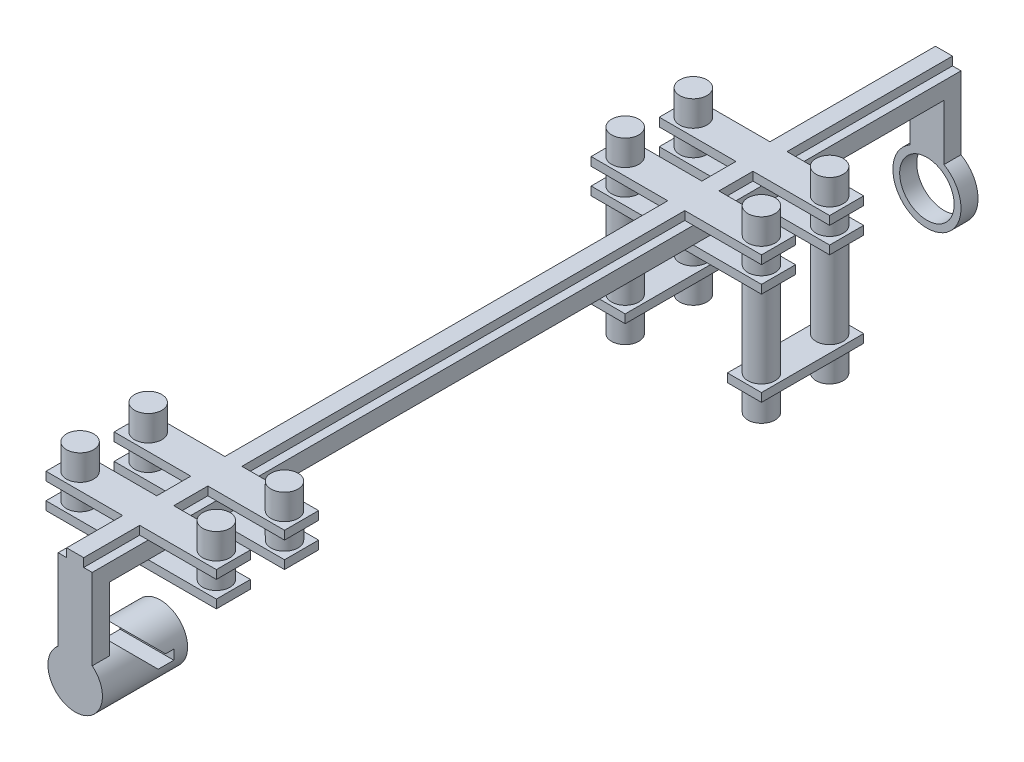
SolidWorks part; units mm, degrees
note: The reader was unsure of these and kept them because the rebuilt part matched: shared geometry of "Sketch9<2>", "Sketch11<2>".
ref_plane "Front Plane" through (0, 0, 0) normal (0, 0, 1) x (1, 0, 0)
ref_plane "Top Plane" through (0, 0, 0) normal (0, 1, 0) x (1, 0, 0)
ref_plane "Right Plane" through (0, 0, 0) normal (1, 0, 0) x (0, 0, -1)
sketch "Sketch1" plane through (0, 0, 0) normal (0, 0, 1) x (1, 0, 0)
  line L0 (0, 10) -> (0, 30)
  line L1 (-5, 30) -> (5, 30)
  line L2 (5, 30) -> (5, 8.6603)
  line L3 (-5, 30) -> (-5, 8.6603)
  circle A0 centre (0, 0) radius 8
  circle A1 centre (0, 0) radius 10
  point P8 (0, 30)
  dimension "D1" = 16
  dimension "D2" = 20
  dimension "D3" = 20
  dimension "D4" = 10
extrude "Boss-Extrude1" add sketch "Sketch1" along normal blind 5 contours A1 A0 | A1 L0 L1 L3 | A1 L2 L1 L0
sketch "Sketch2" plane through (0, 0, 5) normal (0, 0, 1) x (1, 0, 0)
  line L0 (5, 30) -> (5, 8.6603) construction
  line L1 (-5, 30) -> (5, 30)
  line L2 (-5, 30) -> (-5, 25)
  line L3 (-5, 25) -> (5, 25)
  line L4 (5, 30) -> (5, 25)
  dimension "D1" = 5
extrude "Boss-Extrude2" add sketch "Sketch2" along normal blind 250
sketch "Sketch4" plane through (0, 0, 255) normal (0, 0, 1) x (1, 0, 0)
  line L0 (-5, 25) -> (5, 25)
  line L1 (5, 25) -> (5, 6.245)
  line L2 (-5, 25) -> (-5, 6.245)
  arc A0 (-5, 6.245) -> (5, 6.245) centre (0, 0) ccw
extrude "Boss-Extrude3" add sketch "Sketch4" against normal blind 5
sketch "Sketch5" plane through (0, 0, 250) normal (0, 0, -1) x (-1, 0, 0)
  circle A0 centre (0, 0) radius 8
extrude "Boss-Extrude4" add sketch "Sketch5" along normal blind 20
sketch "Sketch6" plane through (0, 0, 0) normal (1, 0, 0) x (0, 0, -1)
  line L0 (-248.5853, 8.66) -> (-243.5853, 8.66)
  line L1 (-243.5853, 8.66) -> (-234.9253, 0)
  line L2 (-248.5853, 8.66) -> (-239.9253, 0)
  line L3 (-240.6367, 0) -> (-237.6205, 0) construction
  line L4 (-239.9253, 0) -> (-238.5099, -1.4155)
  line L5 (-239.9253, 1.4155) -> (-233.9253, 1.4155)
  line L6 (-239.9253, 1.4155) -> (-239.9253, -1.4155)
  line L7 (-239.9253, -1.4155) -> (-233.9253, -1.4155)
  line L8 (-233.9253, 1.4155) -> (-233.9253, -1.4155)
  point P5 (-239.9253, 0)
  dimension "D1" = 5
  dimension "D2" = 45
  dimension "D3" = 1
extrude "Cut-Extrude1" cut sketch "Sketch6" against normal through all both and the other way through all contours L3 L4 L7 L8 | L6 L5 L1 L0 L2 | L1 L3 L8 L5 | L6 L3 L1 L5
sketch "Sketch7" plane through (0, 25, 0) normal (0, -1, 0) x (1, 0, 0)
  line L3 (2.5, 19.6513) -> (5, 19.6513) construction
  line L4 (-2.5, 255) -> (2.5, 255)
  line L5 (-2.5, 255) -> (-2.5, 0)
  line L6 (-2.5, 0) -> (2.5, 0)
  line L7 (2.5, 255) -> (2.5, 0)
  line L8 (5, 250) -> (5, 5) construction
  line L9 (-5, 19.6513) -> (-2.5, 19.6513) construction
  line L10 (-5, 250) -> (-5, 5) construction
  line L17 (-10, 0) -> (10, 0) construction
  line L18 (8, 255) -> (-8, 255) construction
  point P12 (1.6803, 19.6513)
  dimension "D1" = 5
extrude "Boss-Extrude5" add sketch "Sketch7" along normal mid plane 10 from offset 2.5 offset against normal yes
sketch "Sketch8" plane through (0, 32.5, 0) normal (0, 1, 0) x (1, 0, 0)
  line L0 (-2.5, -73.5651) -> (2.5, -73.5651)
  line L1 (-2.5, -255) -> (-2.5, 0) construction
  line L2 (2.5, 0) -> (2.5, -255) construction
sketch "Sketch9" plane through (0, 30, 0) normal (0, 1, 0) x (1, 0, 0)
  line L1 (-25, -68.5651) -> (25, -68.5651)
  line L2 (-25, -68.5651) -> (-25, -78.5651)
  line L3 (-25, -78.5651) -> (25, -78.5651)
  line L4 (25, -68.5651) -> (25, -78.5651)
  line L6 (-2.5, -73.5651) -> (2.5, -73.5651) construction
  line L7 (0, -42.7782) -> (0, -46.0865) construction
  point P5 (0, -68.5651)
  point P8 (25, -73.5651)
  dimension "D1" = 10
  dimension "D2" = 50
extrude "Boss-Extrude6" add sketch "Sketch9" along normal up to surface (2.5 mm away) up to face at (0, 32.5, 127.5)
extrude "Boss-Extrude7" add sketch "Sketch9<2>" against normal up to surface (2.5 mm away) from surface at -5 up to face at (0, 22.5, 127.5) starting at face at (3.75, 25, 127.5)
sketch "Sketch9<2>" plane through (0, 30, 0) normal (0, 1, 0) x (1, 0, 0) same geometry as "Sketch9"
sketch "Sketch10" plane through (0, 25, 0) normal (0, 1, 0) x (1, 0, 0)
  line L0 (-2.5, -68.5651) -> (2.5, -68.5651) construction
  line L2 (-2.5, -78.5651) -> (2.5, -78.5651)
  line L3 (0, -78.5651) -> (0, -68.5651) construction
  line L4 (-20, -73.5651) -> (20, -73.5651) construction
  circle A0 centre (20, -73.5651) radius 4
  circle A1 centre (-20, -73.5651) radius 4
  point P12 (0, -73.5651)
  point P13 (0, -73.5651)
  dimension "D1" = 40
extrude "Boss-Extrude8" add sketch "Sketch10" along normal blind 15 contours A0 | A1
pattern_linear "LPattern1" count 2 spacing 160 along (0, 0, 1) of "Boss-Extrude8", "Boss-Extrude6", "Boss-Extrude7"
pattern_linear "LPattern2" count 2 spacing 20 along (0, 0, -1) of "Boss-Extrude7", "Boss-Extrude8", "Boss-Extrude6"
pattern_linear "LPattern3" count 2 spacing 20 along (0, 0, -1) of "LPattern1"
sketch "Sketch11" plane through (0, 22.5, 0) normal (0, -1, 0) x (1, 0, 0)
  circle A0 centre (-20, 73.5651) radius 4
  circle A1 centre (20, 73.5651) radius 4
  circle A2 centre (20, 53.5651) radius 4
  circle A3 centre (-20, 53.5651) radius 4
extrude "Boss-Extrude9" add sketch "Sketch11" along normal blind 25
sketch "Sketch12" plane through (0, -2.5, 0) normal (0, -1, 0) x (1, 0, 0)
  line L1 (25, 78.5651) -> (25, 48.5651)
  line L11 (-25, 48.5651) -> (-25, 78.5651)
  line L12 (-25, 78.5651) -> (-15, 78.5651)
  line L13 (-25, 78.5651) -> (-2.5, 78.5651) construction
  line L14 (-15, 78.5651) -> (-15, 48.5651)
  line L15 (-2.5, 48.5651) -> (-25, 48.5651) construction
  line L16 (-15, 48.5651) -> (-25, 48.5651)
  line L17 (25, 78.5651) -> (15, 78.5651)
  line L18 (2.5, 78.5651) -> (25, 78.5651) construction
  line L19 (15, 78.5651) -> (15, 48.5651)
  line L20 (25, 48.5651) -> (2.5, 48.5651) construction
  line L21 (15, 48.5651) -> (25, 48.5651)
extrude "Boss-Extrude10" add sketch "Sketch12" along normal blind 2.5
extrude "Boss-Extrude11" add sketch "Sketch11<2>" along normal blind 7.5 from surface at 27.5 starting at face at (-20, -5, 63.5651)
sketch "Sketch11<2>" plane through (0, 22.5, 0) normal (0, -1, 0) x (1, 0, 0) same geometry as "Sketch11"
